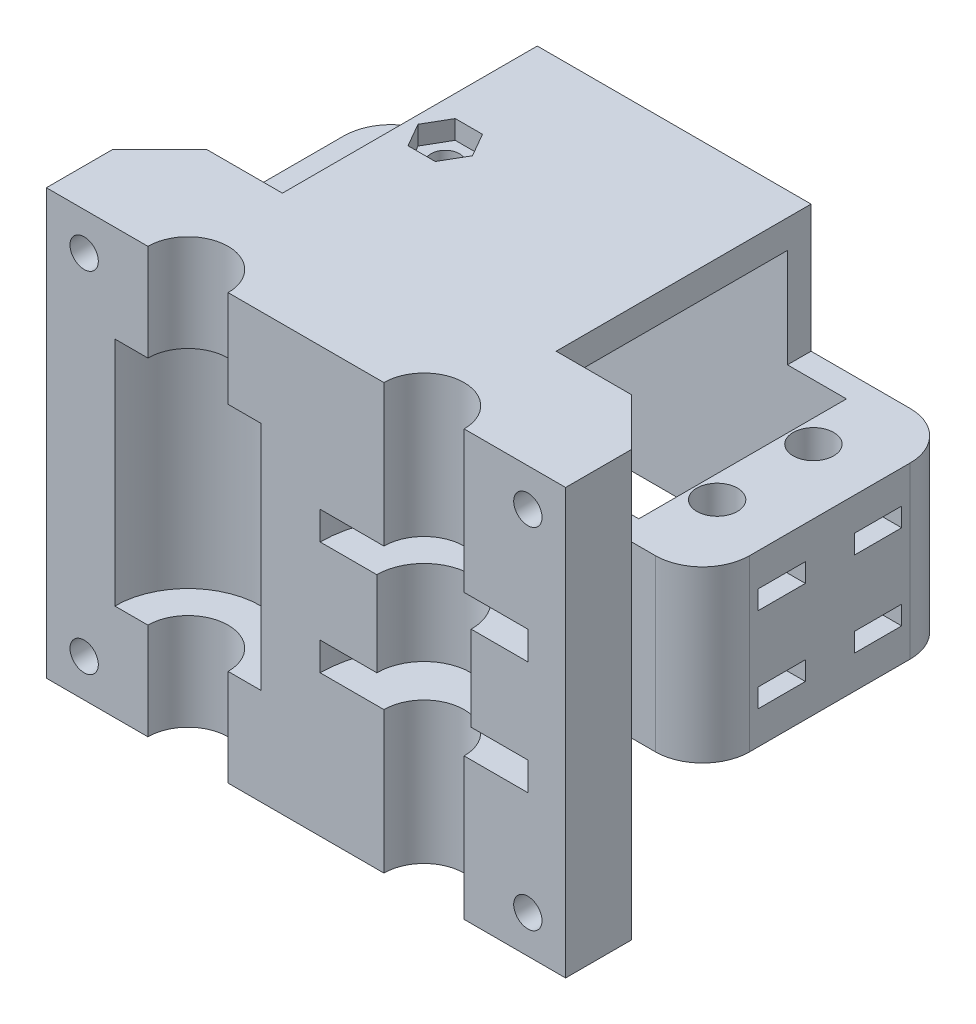
SolidWorks part; units mm, degrees
ref_plane "Plan de face" through (0, 0, 0) normal (0, 0, 1) x (1, 0, 0)
ref_plane "Plan de dessus" through (0, 0, 0) normal (0, 1, 0) x (1, 0, 0)
ref_plane "Plan de droite" through (0, 0, 0) normal (1, 0, 0) x (0, 0, -1)
sketch "Esquisse1" plane through (0, 0, 0) normal (0, 0, 1) x (1, 0, 0)
  line L1 (-27.5, -22.5) -> (27.5, -22.5)
  line L2 (-27.5, -22.5) -> (-27.5, 22.5)
  line L3 (-27.5, 22.5) -> (27.5, 22.5)
  line L4 (27.5, -22.5) -> (27.5, 22.5)
  line L5 (-27.5, -22.5) -> (27.5, 22.5) construction
  line L6 (-27.5, 22.5) -> (27.5, -22.5) construction
  point P0 (0, 0)
  dimension "D1" = 55
  dimension "D2" = 45
extrude "Boss.-Extru.1" add sketch "Esquisse1" along normal blind 12
sketch "Esquisse2" plane through (0, 22.5, 0) normal (0, 1, 0) x (1, 0, 0)
  line L0 (27.5, -12) -> (-27.5, -12) construction
  line L1 (-27.5, -12) -> (-27.5, 0) construction
  line L2 (27.5, -12) -> (27.5, 0) construction
  circle A0 centre (-12.5, -12) radius 4.25
  circle A1 centre (12.5, -12) radius 4.25
  dimension "D1" = 8.5
  dimension "D3" = 8.5
  dimension "D2" = 15
  dimension "D4" = 15
extrude "Enlèv. mat.-Extru.1" cut sketch "Esquisse2" against normal through all
ref_plane "Plan2" through (0, 7.5, 0) normal (0, 1, 0) x (1, 0, 0)
sketch "Esquisse3" plane through (0, 0, 0) normal (0, 1, 0) x (1, 0, 0)
  circle A0 centre (-12.5, -12) radius 7.75
  dimension "D1" = 15.5
extrude "Enlèv. mat.-Extru.2" cut sketch "Esquisse3" against normal blind 12.25 and the other way blind 12.25
sketch "Esquisse4" plane through (0, 7.5, 0) normal (0, 1, 0) x (1, 0, 0)
  circle A0 centre (12.5, -12) radius 11
  dimension "D1" = 22
extrude "Enlèv. mat.-Extru.3" cut sketch "Esquisse4" against normal blind 3
sketch "Esquisse5" plane through (0, 7.5, 0) normal (0, 1, 0) x (1, 0, 0)
  circle A0 centre (12.5, -12) radius 5
  dimension "D1" = 10
extrude "Enlèv. mat.-Extru.4" cut sketch "Esquisse5" against normal blind 15
chamfer "Chanfrein1" [suppressed] distance 10 angle 45
sketch "Esquisse6" plane through (0, 0, 0) normal (0, 0, -1) x (-1, 0, 0)
  line L0 (0, -22.5) -> (0, 22.5) construction
  line L1 (27.5, -22.5) -> (-27.5, -22.5) construction
  line L2 (-27.5, 22.5) -> (27.5, 22.5) construction
  line L3 (27.5, 22.5) -> (27.5, -22.5) construction
  line L4 (27.5, 0) -> (-27.5, 0) construction
  line L5 (-27.5, -22.5) -> (-27.5, 22.5) construction
  circle A0 centre (23.5, -18.5) radius 1.5
  circle A1 centre (-23.5, -18.5) radius 1.5
  circle A2 centre (-23.5, 18.5) radius 1.5
  circle A3 centre (23.5, 18.5) radius 1.5
  dimension "D1" = 3
  dimension "D2" = 4
  dimension "D3" = 4
extrude "Enlèv. mat.-Extru.5" cut sketch "Esquisse6" against normal through all both and the other way through all
sketch "Esquisse7" plane through (0, 0, 0) normal (0, 0, -1) x (-1, 0, 0)
  line L0 (0, -22.5) -> (0, 22.5) construction
  line L1 (27.5, -22.5) -> (-27.5, -22.5) construction
  line L2 (-27.5, 22.5) -> (27.5, 22.5) construction
  line L3 (27.5, 0) -> (-27.5, 0) construction
  line L4 (27.5, 22.5) -> (27.5, -22.5) construction
  line L5 (-27.5, -22.5) -> (-27.5, 22.5) construction
  circle A0 centre (23.5, -18.5) radius 2.5
  circle A1 centre (23.5, 18.5) radius 2.5
  circle A2 centre (-23.5, 18.5) radius 2.5
  circle A3 centre (-23.5, -18.5) radius 2.5
  dimension "D1" = 5
extrude "Enlèv. mat.-Extru.6" cut sketch "Esquisse7" against normal blind 4
chamfer "Chanfrein3" distance 5 angle 45 2 edges at (27.5, 0, 0) (-27.5, 0, 0)
mirror "Symétrie2" about plane through (0, 0, 0) normal (0, 1, 0) of "Enlèv. mat.-Extru.3"
sketch "Esquisse8" plane through (0, 0, 0) normal (0, 0, -1) x (-1, 0, 0)
  line L0 (22.5, -22.5) -> (-22.5, -22.5) construction
  line L1 (-8.5398, -45.608) -> (8.5398, -45.608)
  line L2 (-8.5398, -45.608) -> (-8.5398, 0.608)
  line L3 (-8.5398, 0.608) -> (8.5398, 0.608)
  line L4 (8.5398, -45.608) -> (8.5398, 0.608)
  line L5 (-8.5398, -45.608) -> (8.5398, 0.608) construction
  line L6 (-8.5398, 0.608) -> (8.5398, -45.608) construction
  point P0 (0, -22.5)
sketch "Esquisse9" plane through (0, 0, 0) normal (0, 0, -1) x (-1, 0, 0)
  line L1 (-30, -9) -> (30, -9)
  line L2 (-30, -9) -> (-30, 9)
  line L3 (-30, 9) -> (30, 9)
  line L4 (30, -9) -> (30, 9)
  line L5 (-30, -9) -> (30, 9) construction
  line L6 (-30, 9) -> (30, -9) construction
  point P0 (0, 0)
  dimension "D1" = 18
  dimension "D2" = 60
extrude "Boss.-Extru.2" add sketch "Esquisse9" along normal blind 27
sketch "Esquisse10" plane through (0, 9, 0) normal (0, 1, 0) x (1, 0, 0)
  line L0 (30, 0) -> (-30, 27) construction
  line L2 (-20.75, 24.5) -> (20.75, 24.5)
  line L3 (-20.75, 24.5) -> (-20.75, 2.5)
  line L4 (-20.75, 2.5) -> (20.75, 2.5)
  line L5 (20.75, 24.5) -> (20.75, 2.5)
  line L6 (-20.75, 24.5) -> (20.75, 2.5) construction
  line L7 (-20.75, 2.5) -> (20.75, 24.5) construction
  point P4 (0, 13.5)
  dimension "D1" = 22
  dimension "D2" = 41.5
extrude "Enlèv. mat.-Extru.7" cut sketch "Esquisse10" against normal blind 30
sketch "Esquisse11" plane through (0, -9, 0) normal (0, -1, 0) x (-1, 0, 0)
  circle A0 centre (-23.15, 8.4) radius 2.15
  circle A1 centre (-23.15, 18.6) radius 2.15
  circle A2 centre (24.65, 8.4) radius 2.15
  circle A3 centre (24.65, 18.6) radius 2.15
  dimension "D1" = 4.3
  dimension "D2" = 4.3
extrude "Enlèv. mat.-Extru.8" cut sketch "Esquisse11" against normal through all
fillet "Congé2" radius 5 2 edges at (-30, 0, 0) (30, 0, 0)
fillet "Congé3" radius 5 2 edges at (30, 0, -27) (-30, 0, -27)
sketch "Esquisse12" plane through (30, 0, 0) normal (1, 0, 0) x (0, 0, -1)
  line L0 (6.25, 9) -> (10.55, 9) construction
  line L1 (8.4, 9) -> (8.4, -9) construction
  line L2 (0, -9) -> (5, -9) construction
  line L3 (5, 9) -> (0, 9) construction
  line L4 (10.55, -9) -> (10.55, 9) construction
  line L5 (13.5, 9) -> (13.5, -9) construction
  line L6 (5.9, 3.5) -> (10.9, 3.5)
  line L7 (5.9, 3.5) -> (5.9, 5.5)
  line L8 (5.9, 5.5) -> (10.9, 5.5)
  line L9 (10.9, 3.5) -> (10.9, 5.5)
  line L10 (5.9, 3.5) -> (10.9, 5.5) construction
  line L11 (5.9, 5.5) -> (10.9, 3.5) construction
  line L12 (22, 9) -> (5, 9) construction
  line L13 (22, -9) -> (5, -9) construction
  line L14 (21.1, 3.5) -> (21.1, 5.5)
  line L15 (21.1, 3.5) -> (16.1, 3.5)
  line L16 (21.1, 5.5) -> (16.1, 5.5)
  line L17 (16.1, 3.5) -> (16.1, 5.5)
  point P17 (8.4, 4.5)
  dimension "D1" = 5
  dimension "D2" = 2
  dimension "D3" = 7
extrude "Enlèv. mat.-Extru.9" cut sketch "Esquisse12" against normal blind 9
mirror "Symétrie3" about plane through (0, 0, 0) normal (1, 0, 0) of "Enlèv. mat.-Extru.9"
mirror "Symétrie4" about plane through (0, 0, 0) normal (0, 1, 0) of "Symétrie3", "Enlèv. mat.-Extru.9"
sketch "Esquisse13" plane through (0, 0, 0) normal (0, 0, -1) x (-1, 0, 0)
  line L0 (-14.5, 22.5) -> (14.5, 22.5)
  line L1 (-14.5, 22.5) -> (-14.5, 19.5)
  line L2 (14.5, 22.5) -> (14.5, 19.5)
  line L3 (-14.5, 19.5) -> (14.5, 19.5)
  line L4 (22.5, 9) -> (22.5, 16.2087) construction
  line L5 (-22.5, 22.5) -> (22.5, 22.5) construction
  line L6 (-22.5, 22.5) -> (-22.5, 20.7913) construction
  dimension "D1" = 3
  dimension "D2" = 8
  dimension "D3" = 8
extrude "Boss.-Extru.3" add sketch "Esquisse13" along normal up to surface (27 mm away) up to face at (0, 0, -27)
sketch "Esquisse14" plane through (0, 9, 0) normal (0, 1, 0) x (1, 0, 0)
  line L0 (-14.5, 27) -> (14.5, 27)
  line L1 (-14.5, 27) -> (-14.5, 24.5)
  line L2 (14.5, 27) -> (14.5, 24.5)
  line L3 (-14.5, 24.5) -> (14.5, 24.5)
  line L4 (-25, 27) -> (25, 27) construction
  line L5 (20.75, 24.5) -> (-20.75, 24.5) construction
  line L6 (14.5, 27) -> (14.5, 0) construction
  line L7 (-14.5, 27) -> (-14.5, 0) construction
extrude "Boss.-Extru.4" add sketch "Esquisse14" along normal up to next
sketch "Esquisse15" plane through (0, 22.5, 0) normal (0, 1, 0) x (1, 0, 0)
  circle A0 centre (-10.75, 13.5) radius 1.5
  dimension "D1" = 3
extrude "Enlèv. mat.-Extru.10" cut sketch "Esquisse15" against normal blind 9
sketch "Esquisse16" plane through (0, 22.5, 0) normal (0, 1, 0) x (1, 0, 0)
  line L0 (14.5, 27) -> (-14.5, 27) construction
  line L1 (-9.3066, 16) -> (-12.1934, 16)
  line L2 (-12.1934, 16) -> (-13.6368, 13.5)
  line L3 (-13.6368, 13.5) -> (-12.1934, 11)
  line L4 (-12.1934, 11) -> (-9.3066, 11)
  line L5 (-9.3066, 11) -> (-7.8632, 13.5)
  line L6 (-7.8632, 13.5) -> (-9.3066, 16)
  circle A0 centre (-10.75, 13.5) radius 2.5 construction
  dimension "D1" = 5
extrude "Enlèv. mat.-Extru.11" cut sketch "Esquisse16" against normal blind 2
